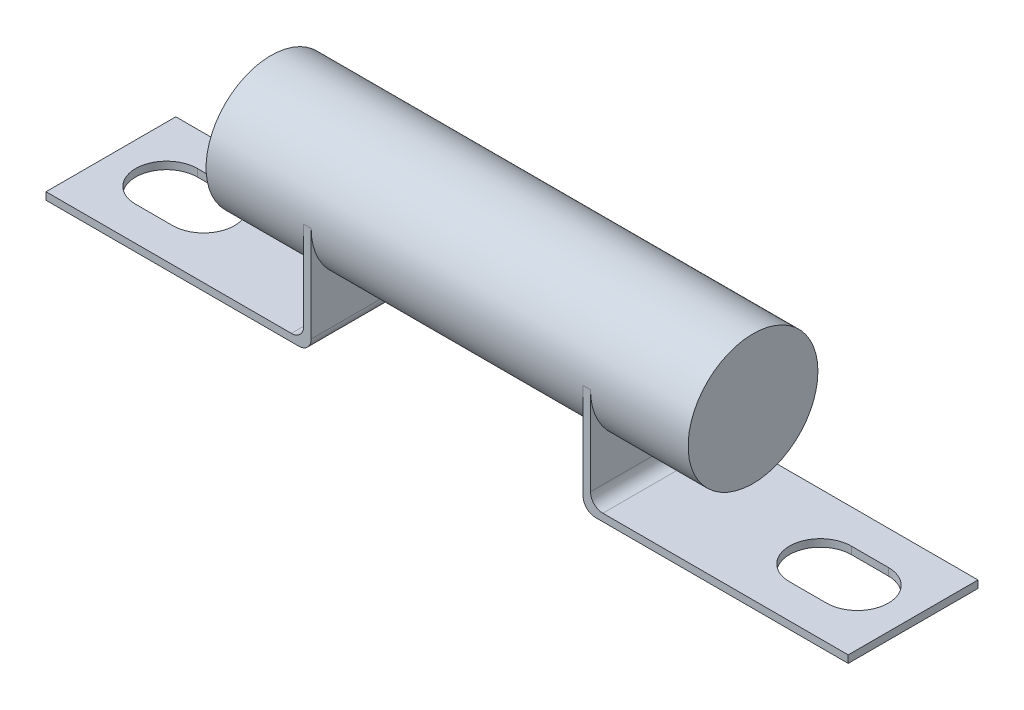
SolidWorks part; units mm, degrees
ref_plane "Front Plane" through (0, 0, 0) normal (0, 0, 1) x (1, 0, 0)
ref_plane "Top Plane" through (0, 0, 0) normal (0, 1, 0) x (1, 0, 0)
ref_plane "Right Plane" through (0, 0, 0) normal (1, 0, 0) x (0, 0, -1)
sketch "Sketch1" plane through (0, 0, 0) normal (1, 0, 0) x (0, 0, -1)
  circle A0 centre (0, 0) radius 5.25
  dimension "D1" = 10.5
extrude "Boss-Extrude1" add sketch "Sketch1" along normal mid plane 39
ref_plane "Plane1" through (0, 0, 5.25) normal (0, 0, 1) x (1, 0, 0)
sketch "Sketch2" plane through (0, 0, 5.25) normal (0, 0, 1) x (1, 0, 0)
  line L0 (0, -5.775) -> (0, 5.775) construction
  line L1 (-32.45, -8.15) -> (-11.6, -8.15)
  line L2 (32.45, -8.15) -> (11.6, -8.15)
  line L3 (-11.6, -8.15) -> (-11.6, 0)
  line L4 (11.6, -8.15) -> (11.6, 0)
  line L5 (-11.6, 0) -> (-11, 0)
  line L6 (11.6, 0) -> (11, 0)
  line L11 (-11, -8.75) -> (-32.45, -8.75)
  line L12 (11, -8.75) -> (32.45, -8.75)
  line L13 (-32.45, -8.75) -> (-32.45, -8.15)
  line L14 (32.45, -8.75) -> (32.45, -8.15)
  line L15 (5.775, 0) -> (-5.775, 0) construction
  line L16 (19.5, 5.25) -> (-19.5, 5.25) construction
  line L17 (-11, 0) -> (-11, -8.75)
  line L18 (11, 0) -> (11, -8.75)
  line L19 (-19.5, 5.25) -> (-19.5, -5.25) construction
  dimension "D1" = 0
  dimension "D2" = 14
  dimension "D3" = 0.6
  dimension "D4" = 64.9
  dimension "D5" = 8.5
ref_plane "Plane2" through (0, 0, -5.25) normal (0, 0, -1) x (-1, 0, 0)
extrude "Boss-Extrude2" add sketch "Sketch2" against normal up to surface (10.5 mm away) up to plane "Plane2"
fillet "Fillet1" radius 1 4 edges at (11, -8.75, 0) (11.6, -8.15, 0) (-11, -8.75, 0) (-11.6, -8.15, 0)
sketch "Sketch3" plane through (0, -8.15, 0) normal (0, 1, 0) x (1, 0, 0)
  line L0 (-24.95, 0) -> (-27.95, 0) construction
  line L1 (-24.95, -2.5) -> (-27.95, -2.5)
  line L2 (-24.95, 2.5) -> (-27.95, 2.5)
  line L3 (0, -5.775) -> (0, 5.775) construction
  line L4 (24.95, 0) -> (27.95, 0) construction
  line L5 (24.95, -2.5) -> (27.95, -2.5)
  line L6 (24.95, 2.5) -> (27.95, 2.5)
  arc A0 (-24.95, -2.5) -> (-24.95, 2.5) centre (-24.95, 0) ccw
  arc A1 (-27.95, 2.5) -> (-27.95, -2.5) centre (-27.95, 0) ccw
  arc A2 (24.95, -2.5) -> (24.95, 2.5) centre (24.95, 0) cw
  arc A3 (27.95, 2.5) -> (27.95, -2.5) centre (27.95, 0) cw
  point P3 (-26.45, 0)
  point P8 (-30.45, 0)
  point P9 (-22.45, 0)
  point P14 (26.45, 0)
  dimension "D1" = 5
  dimension "D2" = 8
  dimension "D3" = 52.9
extrude "Cut-Extrude1" cut sketch "Sketch3" against normal up to surface (0.6 mm away) up to face at (-22.225, -8.75, 0)
